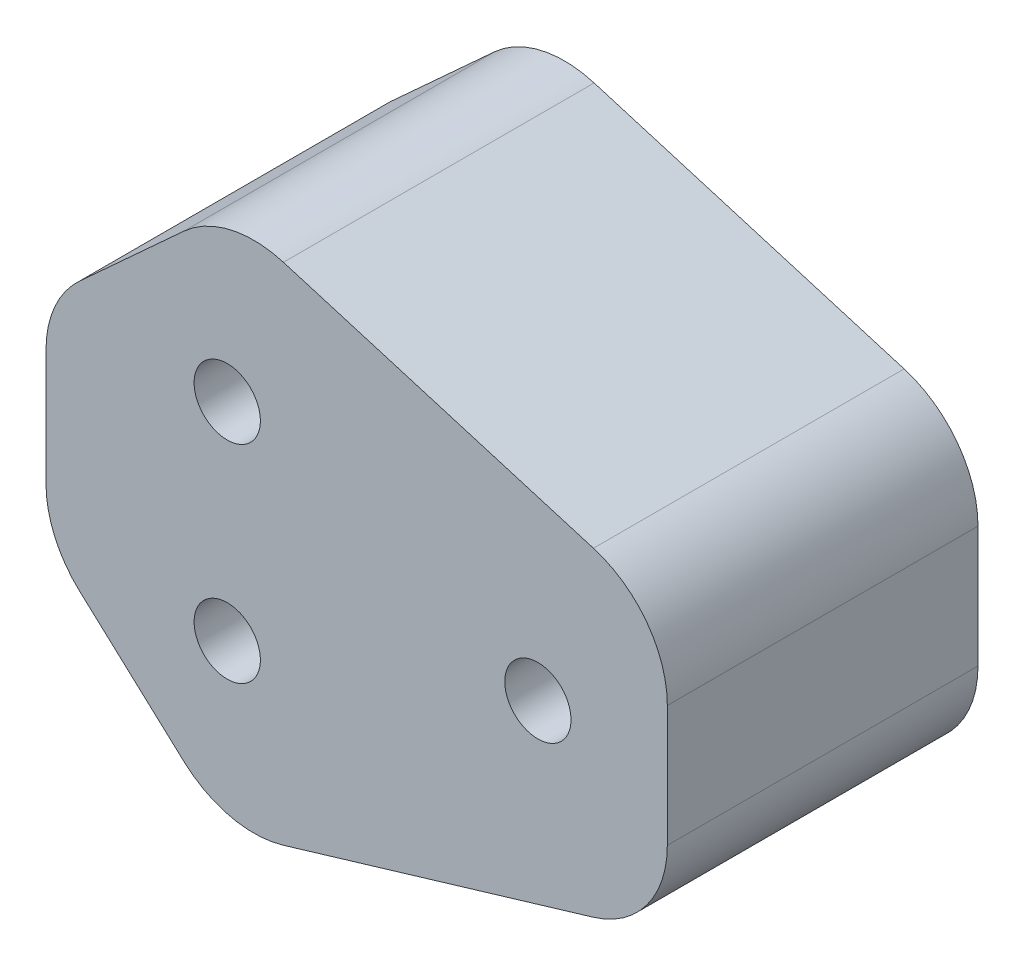
SolidWorks part; units mm, degrees
ref_plane "Front Plane" through (0, 0, 0) normal (0, 0, 1) x (1, 0, 0)
ref_plane "Top Plane" through (0, 0, 0) normal (0, 1, 0) x (1, 0, 0)
ref_plane "Right Plane" through (0, 0, 0) normal (1, 0, 0) x (0, 0, -1)
sketch "Sketch1" plane through (0, 0, 0) normal (0, 0, 1) x (1, 0, 0)
  line L0 (0, 0) -> (0, 12.7)
  line L1 (0, 12.7) -> (11.1125, 22.86)
  line L3 (11.1125, 22.86) -> (38.1, 14.7942)
  line L4 (38.1, 14.7942) -> (38.1, -19.05)
  line L5 (11.1125, 12.7) -> (11.1125, 0) construction
  line L6 (11.1125, 6.35) -> (30.1625, 6.35) construction
  line L7 (11.1125, -10.16) -> (38.1, -2.0942)
  line L8 (0, 0) -> (11.1125, -10.16)
  circle A0 centre (11.1125, 12.7) radius 2.032
  circle A1 centre (11.1125, 0) radius 2.032
  circle A2 centre (30.1625, 6.35) radius 2.032
  dimension "D3" = 4.064
  dimension "D1" = 73.36
  dimension "D2" = 38.1
  dimension "D4" = 11.1125
  dimension "D5" = 12.7
  dimension "D6" = 10.16
  dimension "D7" = 19.05
  dimension "D8" = 19.05
extrude "Boss-Extrude1" add sketch "Sketch1" along normal blind 19.05 contours L0 L8 L7 L4 L3 L1 A2 A1 A0 region at (18.6064, 6.35, 0)
fillet "Fillet1" radius 6.35 6 edges at (38.1, 14.7942, 9.525) (11.1125, 22.86, 9.525) (0, 12.7, 9.525) (38.1, -2.0942, 9.525) (11.1125, -10.16, 9.525) (0, 0, 9.525)
